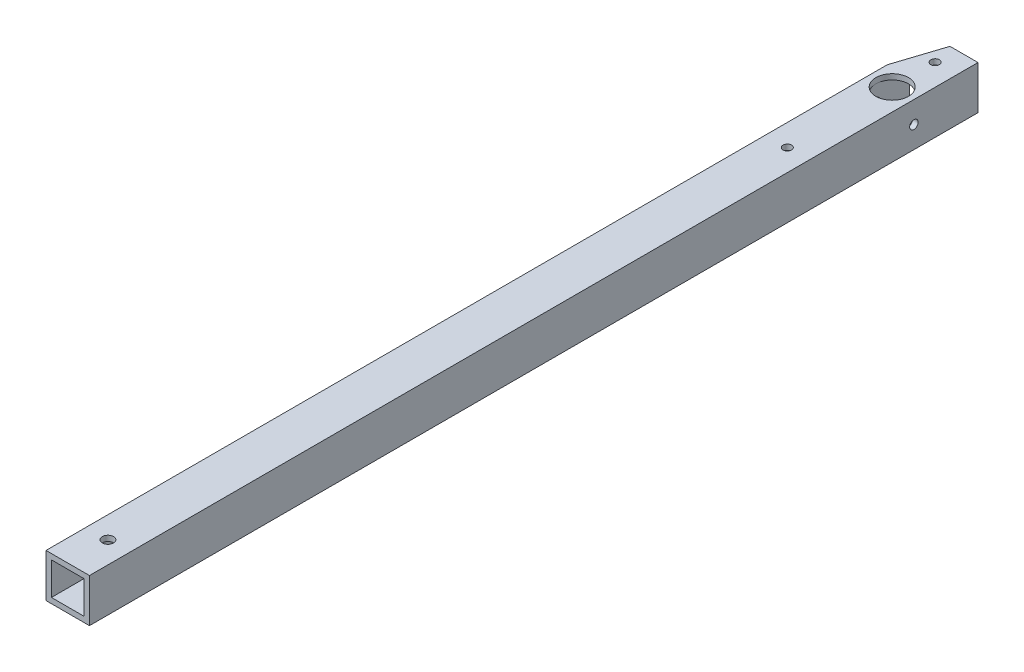
SolidWorks part; units mm, degrees
ref_plane "Front Plane" through (0, 0, 0) normal (0, 0, 1) x (1, 0, 0)
ref_plane "Top Plane" through (0, 0, 0) normal (0, 1, 0) x (1, 0, 0)
ref_plane "Right Plane" through (0, 0, 0) normal (1, 0, 0) x (0, 0, -1)
sketch "Sketch1" plane through (0, 0, 0) normal (0, 0, 1) x (1, 0, 0)
  line L0 (-9.525, 9.525) -> (9.525, 9.525)
  line L2 (-12.7, 12.7) -> (12.7, 12.7)
  line L3 (-12.7, 12.7) -> (-12.7, -12.7)
  line L4 (-12.7, -12.7) -> (12.7, -12.7)
  line L5 (12.7, 12.7) -> (12.7, -12.7)
  line L10 (9.525, 9.525) -> (9.525, -9.525)
  line L11 (-9.525, -9.525) -> (9.525, -9.525)
  line L12 (-9.525, 9.525) -> (-9.525, -9.525)
  point P12 (0, 12.7)
  point P14 (12.7, 0)
  dimension "Wall Thickness" = 3.175
  dimension "Outside Width" = 25.4
  dimension "Outside Height" = 25.4
  dimension "Inside Height" = 19.05
  dimension "Inside Width" = 19.05
sketch "Sketch2" plane through (0, 0, 0) normal (1, 0, 0) x (0, 0, -1)
  line L0 (266.7, 0) -> (-266.7, 0)
  point P4 (0, 0)
  point P7 (-266.7, 0)
  point P10 (266.7, 0)
  dimension "Length" = 533.4
sketch "Sketch3" plane through (0, 0, 0) normal (0, 0, 1) x (1, 0, 0)
  line L21 (12.7, 12.7) -> (-12.7, 12.7)
  line L22 (12.7, -12.7) -> (12.7, 12.7)
  line L23 (-12.7, -12.7) -> (12.7, -12.7)
  line L24 (-12.7, 12.7) -> (-12.7, -12.7)
  line L25 (12.7, 12.7) -> (-12.7, 12.7)
  line L26 (12.7, -12.7) -> (12.7, 12.7)
  line L27 (-12.7, -12.7) -> (12.7, -12.7)
  line L28 (-12.7, 12.7) -> (-12.7, -12.7)
  line L29 (9.525, 9.525) -> (-9.525, 9.525)
  line L30 (9.525, -9.525) -> (9.525, 9.525)
  line L31 (-9.525, -9.525) -> (9.525, -9.525)
  line L32 (-9.525, 9.525) -> (-9.525, -9.525)
  line L33 (9.525, 9.525) -> (-9.525, 9.525)
  line L34 (9.525, -9.525) -> (9.525, 9.525)
  line L35 (-9.525, -9.525) -> (9.525, -9.525)
  line L36 (-9.525, 9.525) -> (-9.525, -9.525)
  dimension "D1" = 0
  dimension "D2" = 0
extrude "Boss-Extrude1" add sketch "Sketch3" along normal up to vertex (266.7 mm away) and the other way up to vertex (266.7 mm away) up to point (0, 0, 266.7) other way up to point (0, 0, -266.7)
sketch "Drawing Reference" plane through (0, 0, 0) normal (1, 0, 0) x (0, 0, -1)
  line L0 (-266.7, 0) -> (266.7, 0) construction
  line L1 (0, -12.7) -> (0, 12.7) construction
  line L2 (-266.7, -12.7) -> (266.7, -12.7) construction
  line L5 (-266.7, 12.7) -> (266.7, 12.7) construction
  point P7 (-248.412, 0)
  point P8 (248.412, 0)
  dimension "D1" = 18.288
sketch "Sketch4" plane through (0, 12.7, 0) normal (0, 1, 0) x (1, 0, 0)
  line L1 (0, 266.7) -> (0, 215.265) construction
  line L7 (-12.7, 225.0135) -> (-12.7, 266.7)
  line L8 (-188.9197, -317.3351) -> (4.6184, 278.3139) construction
  line L10 (-12.7, -266.7) -> (-12.7, 266.7) construction
  line L11 (-12.7, 266.7) -> (12.7, 266.7)
  line L12 (12.7, 266.7) -> (12.7, 252.73)
  line L13 (12.7, -266.7) -> (12.7, 266.7) construction
  line L14 (12.7, 252.73) -> (-3.6943, 252.73)
  line L15 (-3.6943, 252.73) -> (-12.7, 225.0135)
  circle A0 centre (0, 215.265) radius 9.525
  dimension "D1" = 13.97
  dimension "D2" = 51.435
extrude "Cut-Extrude1" cut sketch "Sketch4" against normal blind 25.4
sketch "Sketch5" plane through (0, -12.7, 0) normal (0, -1, 0) x (1, 0, 0)
  circle A0 centre (-0.6587, -179.8767) radius 9.525
extrude "Cut-Extrude2" cut sketch "Sketch5" against normal blind 3.175
sketch "Sketch6" plane through (12.7, 0, 0) normal (1, 0, 0) x (0, 0, -1)
  line L0 (252.73, 0) -> (215.265, 0) construction
  line L1 (252.73, -12.7) -> (252.73, 12.7) construction
  dimension "D1" = 37.465
hole_wizard "#10 Clearance Hole1" positions "Sketch7" profile "Sketch8" hole size "#10" standard "ANSI Inch" end condition through all
sketch "Sketch7" plane through (12.7, 0, 0) normal (1, 0, 0) x (0, 0, -1)
  point P0 (215.265, 0)
sketch "Sketch8" plane through (12.7, 0, -215.265) normal (0, 1, 0) x (0, 0, -1)
  line L0 (0, 0) -> (0, 25.4)
  line L1 (0, 25.4) -> (2.4892, 25.4)
  line L2 (2.4892, 25.4) -> (2.4892, 0)
  line L5 (2.4892, 0) -> (0, 0)
  line L11 (0, -6.35) -> (0, 107.95) construction
  dimension "Thru Hole Dia." = 4.9784
  dimension "Thru Hole Depth" = 25.4
hole_wizard "#10 Clearance Hole2" positions "Sketch9" profile "Sketch10" hole size "#10" standard "ANSI Inch" end condition through all
sketch "Sketch9" plane through (0, 12.7, 0) normal (0, 1, 0) x (1, 0, 0)
  point P0 (0, 153.96)
  point P3 (0, 240.3465)
sketch "Sketch10" plane through (0, 12.7, -153.96) normal (1, 0, 0) x (0, 0, 1)
  line L0 (0, 0) -> (0, 25.4)
  line L1 (0, 25.4) -> (2.4892, 25.4)
  line L2 (2.4892, 25.4) -> (2.4892, 0)
  line L5 (2.4892, 0) -> (0, 0)
  line L11 (0, -6.35) -> (0, 107.95) construction
  dimension "Thru Hole Dia." = 4.9784
  dimension "Thru Hole Depth" = 25.4
hole_wizard "1/4 Clearance Hole2" positions "Sketch13" profile "Sketch14" hole size "1/4" standard "ANSI Inch" end condition through all
sketch "Sketch13" plane through (0, 12.7, 0) normal (0, 1, 0) x (1, 0, 0)
  point P0 (0, -243.2081)
sketch "Sketch14" plane through (0, 12.7, 243.2081) normal (1, 0, 0) x (0, 0, 1)
  line L0 (0, 0) -> (0, 25.4)
  line L1 (0, 25.4) -> (3.2639, 25.4)
  line L2 (3.2639, 25.4) -> (3.2639, 0)
  line L5 (3.2639, 0) -> (0, 0)
  line L11 (0, -6.35) -> (0, 107.95) construction
  dimension "Thru Hole Dia." = 6.5278
  dimension "Thru Hole Depth" = 25.4
equation "\"D1@Drawing Reference\"=\"Outside Width@Sketch1\" * 0.72"
